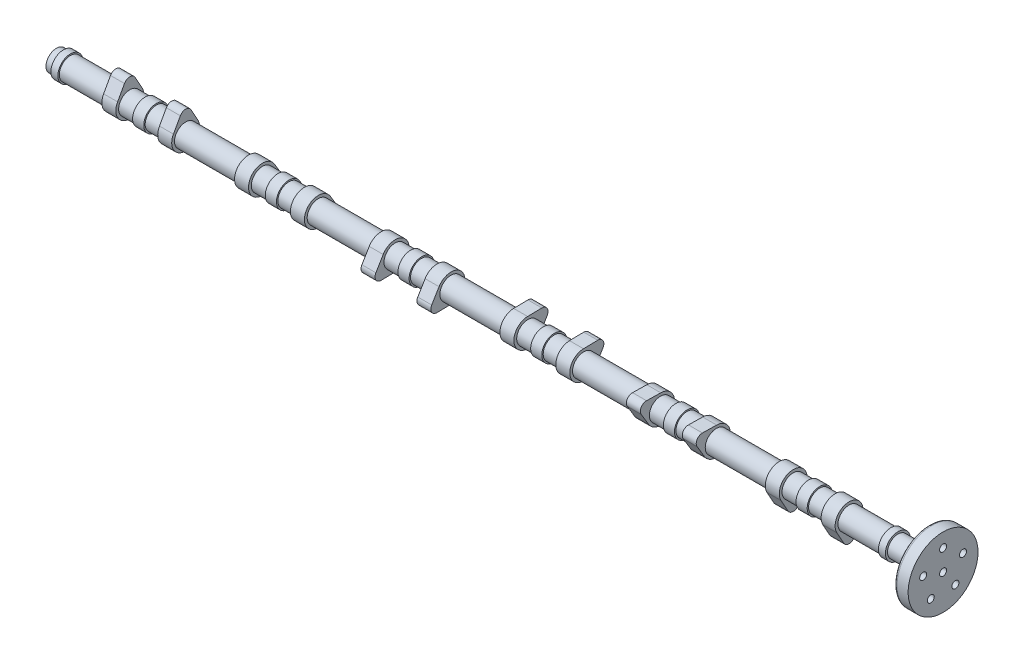
SolidWorks part; units mm, degrees
ref_plane "Front Plane" through (0, 0, 0) normal (0, 0, 1) x (1, 0, 0)
ref_plane "Top Plane" through (0, 0, 0) normal (0, 1, 0) x (1, 0, 0)
ref_plane "Right Plane" through (0, 0, 0) normal (1, 0, 0) x (0, 0, -1)
sketch "Sketch1" plane through (0, 0, 0) normal (1, 0, 0) x (0, 0, -1)
  circle A0 centre (0, 0) radius 8
  dimension "D1" = 16
extrude "Boss-Extrude1" add sketch "Sketch1" along normal mid plane 95
sketch "Sketch2" plane through (0, 0, 0) normal (1, 0, 0) x (0, 0, -1)
  line L0 (0, 0) -> (-8.7462, -4.8481) construction
  line L1 (0, 0) -> (8.7462, -4.8481) construction
  line L2 (0, 0) -> (0, -16) construction
  line L3 (-8.7462, -4.8481) -> (-3.8079, -13.757)
  line L4 (3.8079, -13.757) -> (8.7462, -4.8481)
  arc A0 (8.7462, -4.8481) -> (-8.7462, -4.8481) centre (0, 0) ccw
  arc A1 (-3.8079, -13.757) -> (3.8079, -13.757) centre (0, -11.6462) ccw
  point P9 (0, -16)
  dimension "D1" = 20
  dimension "D2" = 122
  dimension "D3" = 16
extrude "Boss-Extrude2" add sketch "Sketch2" along normal blind 10 from offset 15
mirror "Mirror1" about plane through (0, 0, 0) normal (1, 0, 0) of "Boss-Extrude2"
sketch "Sketch3" plane through (0, 0, 0) normal (1, 0, 0) x (0, 0, -1)
  circle A0 centre (0, 0) radius 9
  dimension "D1" = 18
extrude "Boss-Extrude3" add sketch "Sketch3" along normal mid plane 8
pattern_linear "LPattern1" count 6 spacing 95 along (-1, 0, 0) of bodies 110
move or copy body "Body-Move/Copy1" bodies to move or copy 113 copy no rotation origin (0, 0, 0) rotation axis (-1, 0, 0) rotation angle 60
move or copy body "Body-Move/Copy2" bodies to move or copy 111 copy no rotation origin (0, 0, 0) rotation axis (-1, 0, 0) rotation angle 120
move or copy body "Body-Move/Copy3" bodies to move or copy 114 copy no rotation origin (0, 0, 0) rotation axis (1, 0, 0) rotation angle 60
move or copy body "Body-Move/Copy4" bodies to move or copy 112 copy no rotation origin (0, 0, 0) rotation axis (1, 0, 0) rotation angle 120
move or copy body "Body-Move/Copy5" bodies to move or copy 115 copy no rotation origin (0, 0, 0) rotation axis (1, 0, 0) rotation angle 180
sketch "Sketch4" plane through (-522.5, 0, 0) normal (-1, 0, 0) x (0, 0, 1)
  circle A0 centre (0, 0) radius 8 construction
  circle A1 centre (0, 0) radius 8
extrude "Boss-Extrude4" add sketch "Sketch4" along normal blind 10
sketch "Sketch5" plane through (-532.5, 0, 0) normal (-1, 0, 0) x (0, 0, 1)
  circle A0 centre (0, 0) radius 9
  dimension "D1" = 18
extrude "Boss-Extrude5" add sketch "Sketch5" along normal blind 5
combine bodies "Combine1" operation type add bodies to combine 118 117 116 119 110 122
sketch "Sketch6" plane through (-537.5, 0, 0) normal (-1, 0, 0) x (0, 0, 1)
  circle A0 centre (0, 0) radius 7.5
  dimension "D1" = 15
extrude "Boss-Extrude6" add sketch "Sketch6" along normal blind 5
sketch "Sketch7" plane through (47.5, 0, 0) normal (1, 0, 0) x (0, 0, -1)
  circle A0 centre (0, 0) radius 8 construction
  circle A1 centre (0, 0) radius 8
extrude "Boss-Extrude7" add sketch "Sketch7" along normal blind 7.5
sketch "Sketch8" plane through (55, 0, 0) normal (1, 0, 0) x (0, 0, -1)
  circle A0 centre (0, 0) radius 9
  dimension "D1" = 18
extrude "Boss-Extrude8" add sketch "Sketch8" along normal blind 5
sketch "Sketch9" plane through (60, 0, 0) normal (1, 0, 0) x (0, 0, -1)
  circle A0 centre (0, 0) radius 7.5
  dimension "D1" = 15
extrude "Boss-Extrude9" add sketch "Sketch9" along normal blind 22.3
sketch "Sketch10" plane through (82.3, 0, 0) normal (1, 0, 0) x (0, 0, -1)
  circle A0 centre (0, 0) radius 2.5
  circle A1 centre (0, 0) radius 25
  dimension "D1" = 5
  dimension "D2" = 50
extrude "Boss-Extrude10" add sketch "Sketch10" along normal blind 10
sketch "Sketch11" plane through (92.3, 0, 0) normal (1, 0, 0) x (0, 0, -1)
  circle A0 centre (0, 0) radius 15 construction
  circle A1 centre (0, 15) radius 2.5
  circle A2 centre (0, 0) radius 2.5
  circle A3 centre (14.2658, 4.6353) radius 2.5
  circle A4 centre (8.8168, -12.1353) radius 2.5
  circle A5 centre (-8.8168, -12.1353) radius 2.5
  circle A6 centre (-14.2658, 4.6353) radius 2.5
  point P17 (0, 0)
  dimension "D1" = 30
  dimension "D2" = 5
  dimension "D3" = 5
extrude "Cut-Extrude1" cut sketch "Sketch11" against normal blind 15
fillet "Fillet1" radius 2 2 edges at (82.3, 0, -25) (82.3, 0, -7.5)
